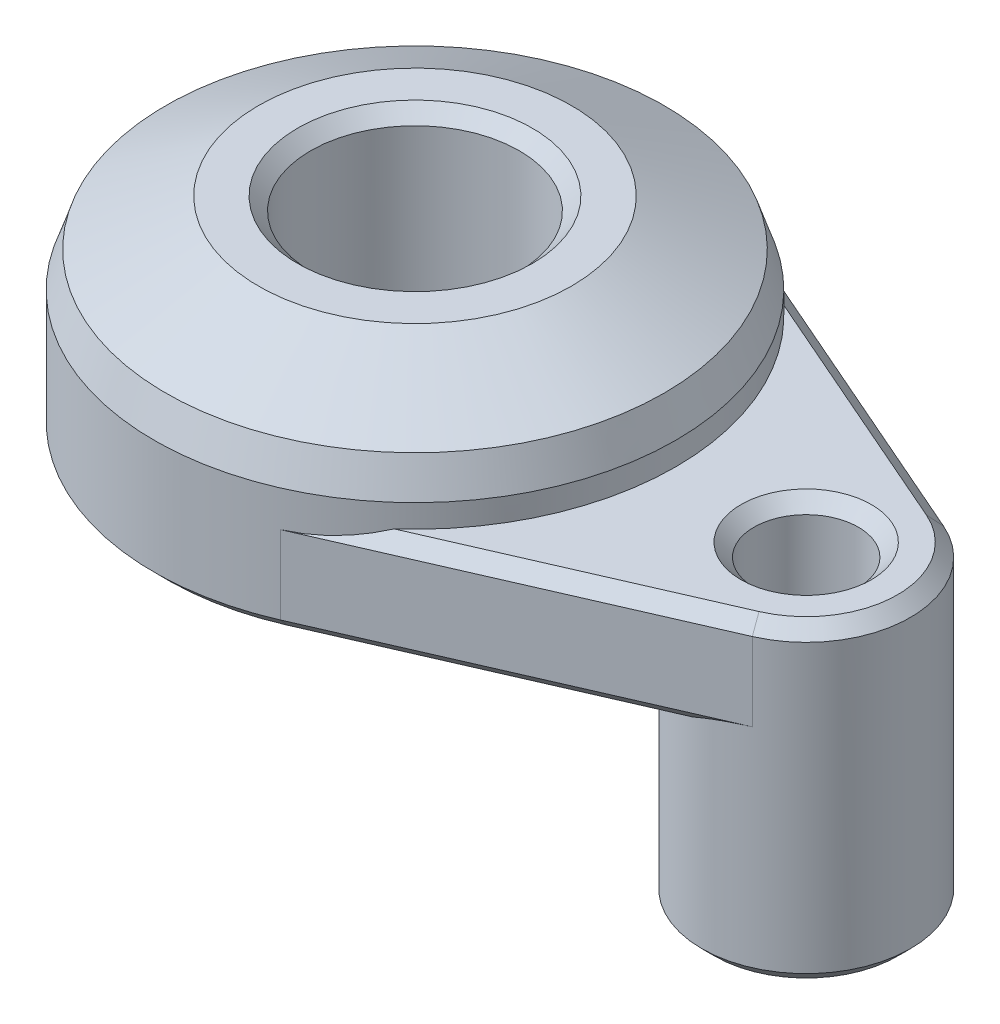
SolidWorks part; units mm, degrees
ref_plane "前视基准面" through (0, 0, 0) normal (0, 0, 1) x (1, 0, 0)
ref_plane "上视基准面" through (0, 0, 0) normal (0, 1, 0) x (1, 0, 0)
ref_plane "右视基准面" through (0, 0, 0) normal (1, 0, 0) x (0, 0, -1)
other "Configuration Table"
sketch "草图1" plane through (0, 0, 0) normal (0, 1, 0) x (1, 0, 0)
  line L0 (0, 0) -> (7.5, 0) construction
  line L1 (2, -4.5826) -> (8.3, -1.833)
  line L2 (8.3, 1.833) -> (2, 4.5826)
  arc A0 (2, 4.5826) -> (2, -4.5826) centre (0, 0) ccw
  arc A1 (8.3, -1.833) -> (8.3, 1.833) centre (7.5, 0) ccw
  dimension "D1" = 10
  dimension "D3" = 4
  dimension "D2" = 7.5
extrude "凸台-拉伸1" add sketch "草图1" along normal blind 2
sketch "草图2" plane through (0, 0, 0) normal (0, 1, 0) x (1, 0, 0)
  arc A0 (8.3, -1.833) -> (8.3, 1.833) centre (7.5, 0) ccw construction
  arc A1 (8.3, -1.833) -> (8.3, 1.833) centre (7.5, 0) ccw construction
  circle A3 centre (7.5, 0) radius 2
extrude "凸台-拉伸2" add sketch "草图2" against normal blind 4
sketch "草图3" plane through (0, 0, 0) normal (0, 1, 0) x (1, 0, 0)
  circle A0 centre (0, 0) radius 1.5
  arc A1 (8.3, -1.833) -> (8.3, 1.833) centre (7.5, 0) ccw construction
  arc A2 (8.3, -1.833) -> (8.3, 1.833) centre (7.5, 0) ccw construction
  circle A3 centre (7.5, 0) radius 1
  dimension "D1" = 3
  dimension "D2" = 2
extrude "切除-拉伸1" cut sketch "草图3" against normal up to surface (4 mm away) from surface up to face at (7.5, -4, 2) starting at face at (3.7, 2, 0)
sketch "草图4" plane through (0, 0, 0) normal (0, 0, 1) x (1, 0, 0)
  line L0 (0, -1000) -> (0, 49000) construction
  line L1 (0, 2) -> (5, 2)
  line L2 (1.5, 2) -> (-1.5, 2) construction
  line L3 (2, 2) -> (8.3, 2) construction
  line L4 (5, 2) -> (5, 3)
  line L5 (5, 3) -> (3, 4)
  line L6 (3, 4) -> (0, 4)
  line L7 (0, 4) -> (0, 2)
  dimension "D1" = 5
  dimension "D2" = 3
  dimension "D3" = 1
  dimension "D4" = 2
revolve "旋转1" add sketch "草图4" angle 360 about L0
chamfer "倒角1" distance 0.25 angle 45 4 edges at (5, 3, 0) (5.15, 0, -3.2078) (5.15, 0, 3.2078) (-5, 0, 0) first distance on face at (3, 4, 0) first distance on face at (0, 0, 1.5)
sketch "草图6" plane through (0, 0, 0) normal (0, 1, 0) x (1, 0, 0)
  circle A0 centre (0, 0) radius 3
  dimension "D1" = 6
extrude "凸台-拉伸3" add sketch "草图6" against normal blind 1.5
chamfer "倒角2" distance 0.25 angle 45 7 edges at (7.5, -4, 2) (7.5, 2, 1) (5.15, 2, 3.2078) (5.15, 2, -3.2078) (9.5, 2, 0) (0, -1.5, 3) (7.5, -4, 1)
sketch "草图7" plane through (0, 0, 0) normal (0, 1, 0) x (1, 0, 0)
  circle A0 centre (0, 0) radius 2
  dimension "D1" = 4
extrude "切除-拉伸2" cut sketch "草图7" along normal up to surface (4 mm away) from surface up to face at (3, 4, 0) starting at face at (0, -1.5, 2.75)
chamfer "倒角3" distance 0.25 angle 45 2 edges at (-2, 4, 0) (0, -1.5, 2)
